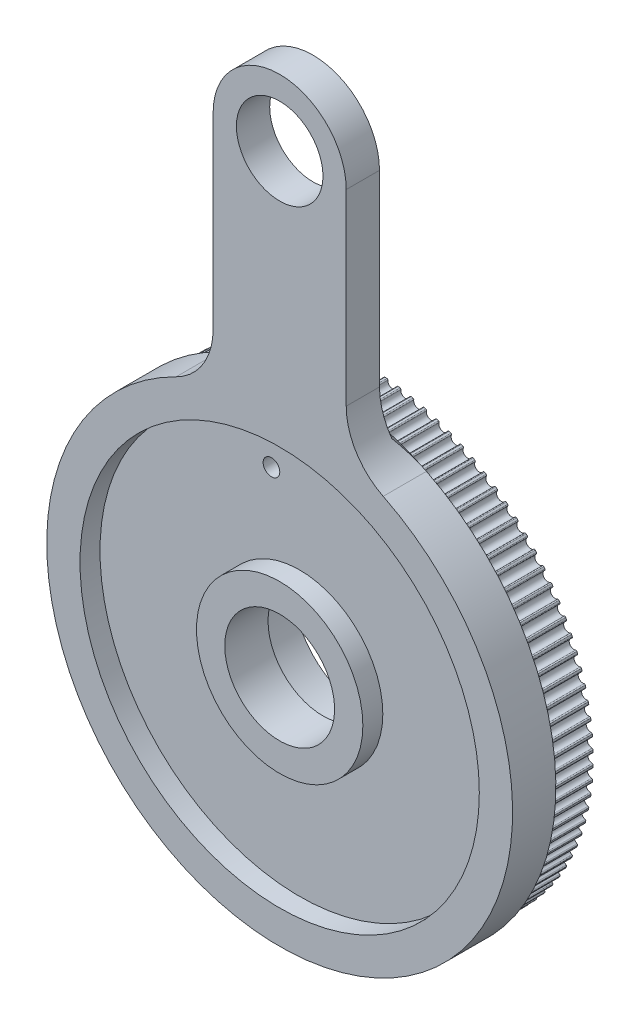
SolidWorks part; units mm, degrees
ref_plane "前视基准面" through (0, 0, 0) normal (0, 0, 1) x (1, 0, 0)
ref_plane "上视基准面" through (0, 0, 0) normal (0, 1, 0) x (1, 0, 0)
ref_plane "右视基准面" through (0, 0, 0) normal (1, 0, 0) x (0, 0, -1)
sketch "草图1" plane through (0, 0, 0) normal (0, 0, 1) x (1, 0, 0)
  line L0 (-10, 68.5) -> (-10, 40.3113)
  line L1 (10, 68.5) -> (10, 40.3113)
  arc A0 (-15.5556, 31.3532) -> (15.5556, 31.3532) centre (0, 0) ccw
  circle A1 centre (0, 0) radius 8.25
  circle A2 centre (0, 68.5) radius 6.5
  arc A3 (10, 68.5) -> (-10, 68.5) centre (0, 68.5) ccw
  arc A4 (10, 40.3113) -> (15.5556, 31.3532) centre (20, 40.3113) ccw
  arc A5 (-10, 40.3113) -> (-15.5556, 31.3532) centre (-20, 40.3113) cw
  dimension "D1" = 70
  dimension "D2" = 16.5
  dimension "D3" = 13
  dimension "D5" = 20
  dimension "D6" = 10
  dimension "D4" = 68.5
extrude "凸台-拉伸1" add sketch "草图1" along normal blind 6.5
sketch "草图2" plane through (0, 0, 6.5) normal (0, 0, 1) x (1, 0, 0)
  circle A0 centre (0, 0) radius 12.5
  circle A1 centre (0, 0) radius 30
  dimension "D1" = 60
  dimension "D2" = 25
extrude "切除-拉伸1" cut sketch "草图2" against normal blind 3
sketch "草图3" plane through (0, 0, 0) normal (0, 0, -1) x (-1, 0, 0)
  line L0 (-10, 40.3113) -> (-10, 68.5) construction
  line L1 (10, 68.5) -> (10, 40.3113) construction
  line L2 (-10, 40.3113) -> (-10, 68.5)
  line L3 (10, 68.5) -> (10, 40.3113)
  arc A1 (10, 68.5) -> (-10, 68.5) centre (0, 68.5) ccw construction
  arc A2 (15.5556, 31.3532) -> (-15.5556, 31.3532) centre (0, 0) ccw
  arc A3 (10, 68.5) -> (-10, 68.5) centre (0, 68.5) ccw
  arc A4 (-15.5556, 31.3532) -> (15.5556, 31.3532) centre (0, 0) ccw construction
  arc A5 (10, 40.3113) -> (15.5556, 31.3532) centre (20, 40.3113) ccw construction
  arc A6 (-15.5556, 31.3532) -> (-10, 40.3113) centre (-20, 40.3113) ccw construction
  arc A7 (10, 40.3113) -> (15.5556, 31.3532) centre (20, 40.3113) ccw
  arc A8 (-15.5556, 31.3532) -> (-10, 40.3113) centre (-20, 40.3113) ccw
extrude "切除-拉伸2" cut sketch "草图3" against normal blind 1.5
chamfer "倒角1" distance 1.5 angle 45 1 edges at (0, 35, 1.5)
sketch "草图4" plane through (0, 0, 0) normal (0, 0, -1) x (-1, 0, 0)
  arc B0 (1.1216, 34.1041) -> (0.8633, 34.1116) centre (0, 0) ccw
  arc B1 (1.2763, 33.9415) -> (1.1216, 34.1041) centre (1.1163, 33.9441) ccw
  arc B2 (0.8633, 34.1116) -> (0.6994, 33.9583) centre (0.8593, 33.9516) ccw
  arc B3 (1.2763, 33.9415) -> (2.6727, 33.8602) centre (1.9762, 33.93) ccw
  arc B4 (-0.8633, 34.1116) -> (-1.1216, 34.1041) centre (0, 0) ccw
  arc B5 (-0.6994, 33.9583) -> (-0.8633, 34.1116) centre (-0.8593, 33.9516) ccw
  arc B6 (-1.1216, 34.1041) -> (-1.2763, 33.9415) centre (-1.1163, 33.9441) ccw
  arc B7 (-0.6994, 33.9583) -> (0.6994, 33.9583) centre (0, 33.9875) ccw
  arc B8 (-2.8453, 34.0037) -> (-3.1027, 33.9812) centre (0, 0) ccw
  arc B9 (-2.6727, 33.8602) -> (-2.8453, 34.0037) centre (-2.8319, 33.8442) ccw
  arc B10 (-3.1027, 33.9812) -> (-3.2477, 33.8099) centre (-3.0881, 33.8218) ccw
  arc B11 (-2.6727, 33.8602) -> (-1.2763, 33.9415) centre (-1.9762, 33.93) ccw
  arc B12 (-4.8176, 33.7807) -> (-5.0732, 33.7433) centre (0, 0) ccw
  arc B13 (-4.637, 33.6475) -> (-4.8176, 33.7807) centre (-4.795, 33.6223) ccw
  arc B14 (-5.0732, 33.7433) -> (-5.208, 33.5638) centre (-5.0494, 33.585) ccw
  arc B15 (-4.637, 33.6475) -> (-3.2477, 33.8099) centre (-3.9457, 33.7577) ccw
  arc B16 (-6.7736, 33.4434) -> (-7.0266, 33.3912) centre (0, 0) ccw
  arc B17 (-6.5856, 33.321) -> (-6.7736, 33.4434) centre (-6.7418, 33.2866) ccw
  arc B18 (-7.0266, 33.3912) -> (-7.1508, 33.2042) centre (-6.9937, 33.2346) ccw
  arc B19 (-6.5856, 33.321) -> (-5.208, 33.5638) centre (-5.9019, 33.4712) ccw
  arc B20 (-8.7067, 32.993) -> (-8.9563, 32.9261) centre (0, 0) ccw
  arc B21 (-8.5119, 32.8817) -> (-8.7067, 32.993) centre (-8.6659, 32.8383) ccw
  arc B22 (-8.9563, 32.9261) -> (-9.0693, 32.7323) centre (-8.9143, 32.7717) ccw
  arc B23 (-8.5119, 32.8817) -> (-7.1508, 33.2042) centre (-7.8381, 33.0714) ccw
  arc B24 (-10.6103, 32.4309) -> (-10.8556, 32.3497) centre (0, 0) ccw
  arc B25 (-10.4094, 32.3311) -> (-10.6103, 32.4309) centre (-10.5606, 32.2789) ccw
  arc B26 (-10.8556, 32.3497) -> (-10.9572, 32.1496) centre (-10.8047, 32.198) ccw
  arc B27 (-10.4094, 32.3311) -> (-9.0693, 32.7323) centre (-9.7477, 32.5597) ccw
  arc B28 (-12.4781, 31.7591) -> (-12.7182, 31.6637) centre (0, 0) ccw
  arc B29 (-12.2716, 31.6712) -> (-12.4781, 31.7591) centre (-12.4196, 31.6102) ccw
  arc B30 (-12.7182, 31.6637) -> (-12.808, 31.4581) centre (-12.6586, 31.5153) ccw
  arc B31 (-12.2716, 31.6712) -> (-10.9572, 32.1496) centre (-11.6244, 31.9378) ccw
  arc B32 (-14.3036, 30.9799) -> (-14.5378, 30.8707) centre (0, 0) ccw
  arc B33 (-14.0924, 30.904) -> (-14.3036, 30.9799) centre (-14.2365, 30.8346) ccw
  arc B34 (-14.5378, 30.8707) -> (-14.6155, 30.6601) centre (-14.4696, 30.7259) ccw
  arc B35 (-14.0924, 30.904) -> (-12.808, 31.4581) centre (-13.4618, 31.2079) ccw
  arc B36 (-16.0807, 30.0958) -> (-16.3081, 29.9731) centre (0, 0) ccw
  arc B37 (-15.8655, 30.0324) -> (-16.0807, 30.0958) centre (-16.0053, 29.9547) ccw
  arc B38 (-16.3081, 29.9731) -> (-16.3735, 29.7584) centre (-16.2317, 29.8326) ccw
  arc B39 (-15.8655, 30.0324) -> (-14.6155, 30.6601) centre (-15.2536, 30.3723) ccw
  arc B40 (-17.8034, 29.1098) -> (-18.0233, 28.9742) centre (0, 0) ccw
  arc B41 (-17.5848, 29.0591) -> (-17.8034, 29.1098) centre (-17.7199, 28.9733) ccw
  arc B42 (-18.0233, 28.9742) -> (-18.0761, 28.7561) centre (-17.9388, 28.8383) ccw
  arc B43 (-17.5848, 29.0591) -> (-16.3735, 29.7584) centre (-16.9937, 29.434) ccw
  arc B44 (-19.4659, 28.0254) -> (-19.6775, 27.8772) centre (0, 0) ccw
  arc B45 (-19.2447, 27.9874) -> (-19.4659, 28.0254) centre (-19.3746, 27.894) ccw
  arc B46 (-19.6775, 27.8772) -> (-19.7175, 27.6564) centre (-19.5853, 27.7465) ccw
  arc B47 (-19.2447, 27.9874) -> (-18.0761, 28.7561) centre (-18.6764, 28.3961) ccw
  arc B48 (-21.0625, 26.8462) -> (-21.2652, 26.6859) centre (0, 0) ccw
  arc B49 (-20.8395, 26.8211) -> (-21.0625, 26.8462) centre (-20.9637, 26.7203) ccw
  arc B50 (-21.2652, 26.6859) -> (-21.2922, 26.4631) centre (-21.1655, 26.5608) ccw
  arc B51 (-20.8395, 26.8211) -> (-19.7175, 27.6564) centre (-20.2959, 27.2622) ccw
  arc B52 (-22.5878, 25.5761) -> (-22.7808, 25.4043) centre (0, 0) ccw
  arc B53 (-22.3637, 25.564) -> (-22.5878, 25.5761) centre (-22.4819, 25.4561) ccw
  arc B54 (-22.7808, 25.4043) -> (-22.7949, 25.1803) centre (-22.674, 25.2852) ccw
  arc B55 (-22.3637, 25.564) -> (-21.2922, 26.4631) centre (-21.8467, 26.0359) ccw
  arc B56 (-24.0367, 24.2194) -> (-24.2194, 24.0367) centre (0, 0) ccw
  arc B57 (-23.8123, 24.2204) -> (-24.0367, 24.2194) centre (-23.924, 24.1059) ccw
  arc B58 (-24.2194, 24.0367) -> (-24.2204, 23.8123) centre (-24.1059, 23.924) ccw
  arc B59 (-23.8123, 24.2204) -> (-22.7949, 25.1803) centre (-23.3236, 24.7216) ccw
  arc B60 (-25.4043, 22.7808) -> (-25.5761, 22.5878) centre (0, 0) ccw
  arc B61 (-25.1803, 22.7949) -> (-25.4043, 22.7808) centre (-25.2852, 22.674) ccw
  arc B62 (-25.5761, 22.5878) -> (-25.564, 22.3637) centre (-25.4561, 22.4819) ccw
  arc B63 (-25.1803, 22.7949) -> (-24.2204, 23.8123) centre (-24.7216, 23.3236) ccw
  arc B64 (-26.6859, 21.2652) -> (-26.8462, 21.0625) centre (0, 0) ccw
  arc B65 (-26.4631, 21.2922) -> (-26.6859, 21.2652) centre (-26.5608, 21.1655) ccw
  arc B66 (-26.8462, 21.0625) -> (-26.8211, 20.8395) centre (-26.7203, 20.9637) ccw
  arc B67 (-26.4631, 21.2922) -> (-25.564, 22.3637) centre (-26.0359, 21.8467) ccw
  arc B68 (-27.8772, 19.6775) -> (-28.0254, 19.4659) centre (0, 0) ccw
  arc B69 (-27.6564, 19.7175) -> (-27.8772, 19.6775) centre (-27.7465, 19.5853) ccw
  arc B70 (-28.0254, 19.4659) -> (-27.9874, 19.2447) centre (-27.894, 19.3746) ccw
  arc B71 (-27.6564, 19.7175) -> (-26.8211, 20.8395) centre (-27.2622, 20.2959) ccw
  arc B72 (-28.9742, 18.0233) -> (-29.1098, 17.8034) centre (0, 0) ccw
  arc B73 (-28.7561, 18.0761) -> (-28.9742, 18.0233) centre (-28.8383, 17.9388) ccw
  arc B74 (-29.1098, 17.8034) -> (-29.0591, 17.5848) centre (-28.9733, 17.7199) ccw
  arc B75 (-28.7561, 18.0761) -> (-27.9874, 19.2447) centre (-28.3961, 18.6764) ccw
  arc B76 (-29.9731, 16.3081) -> (-30.0958, 16.0807) centre (0, 0) ccw
  arc B77 (-29.7584, 16.3735) -> (-29.9731, 16.3081) centre (-29.8326, 16.2317) ccw
  arc B78 (-30.0958, 16.0807) -> (-30.0324, 15.8655) centre (-29.9547, 16.0053) ccw
  arc B79 (-29.7584, 16.3735) -> (-29.0591, 17.5848) centre (-29.434, 16.9937) ccw
  arc B80 (-30.8707, 14.5378) -> (-30.9799, 14.3036) centre (0, 0) ccw
  arc B81 (-30.6601, 14.6155) -> (-30.8707, 14.5378) centre (-30.7259, 14.4696) ccw
  arc B82 (-30.9799, 14.3036) -> (-30.904, 14.0924) centre (-30.8346, 14.2365) ccw
  arc B83 (-30.6601, 14.6155) -> (-30.0324, 15.8655) centre (-30.3723, 15.2536) ccw
  arc B84 (-31.6637, 12.7182) -> (-31.7591, 12.4781) centre (0, 0) ccw
  arc B85 (-31.4581, 12.808) -> (-31.6637, 12.7182) centre (-31.5153, 12.6586) ccw
  arc B86 (-31.7591, 12.4781) -> (-31.6712, 12.2716) centre (-31.6102, 12.4196) ccw
  arc B87 (-31.4581, 12.808) -> (-30.904, 14.0924) centre (-31.2079, 13.4618) ccw
  arc B88 (-32.3497, 10.8556) -> (-32.4309, 10.6103) centre (0, 0) ccw
  arc B89 (-32.1496, 10.9572) -> (-32.3497, 10.8556) centre (-32.198, 10.8047) ccw
  arc B90 (-32.4309, 10.6103) -> (-32.3311, 10.4094) centre (-32.2789, 10.5606) ccw
  arc B91 (-32.1496, 10.9572) -> (-31.6712, 12.2716) centre (-31.9378, 11.6244) ccw
  arc B92 (-32.9261, 8.9563) -> (-32.993, 8.7067) centre (0, 0) ccw
  arc B93 (-32.7323, 9.0693) -> (-32.9261, 8.9563) centre (-32.7717, 8.9143) ccw
  arc B94 (-32.993, 8.7067) -> (-32.8817, 8.5119) centre (-32.8383, 8.6659) ccw
  arc B95 (-32.7323, 9.0693) -> (-32.3311, 10.4094) centre (-32.5597, 9.7477) ccw
  arc B96 (-33.3912, 7.0266) -> (-33.4434, 6.7736) centre (0, 0) ccw
  arc B97 (-33.2042, 7.1508) -> (-33.3912, 7.0266) centre (-33.2346, 6.9937) ccw
  arc B98 (-33.4434, 6.7736) -> (-33.321, 6.5856) centre (-33.2866, 6.7418) ccw
  arc B99 (-33.2042, 7.1508) -> (-32.8817, 8.5119) centre (-33.0714, 7.8381) ccw
  arc B100 (-33.7433, 5.0732) -> (-33.7807, 4.8176) centre (0, 0) ccw
  arc B101 (-33.5638, 5.208) -> (-33.7433, 5.0732) centre (-33.585, 5.0494) ccw
  arc B102 (-33.7807, 4.8176) -> (-33.6475, 4.637) centre (-33.6223, 4.795) ccw
  arc B103 (-33.5638, 5.208) -> (-33.321, 6.5856) centre (-33.4712, 5.9019) ccw
  arc B104 (-33.9812, 3.1027) -> (-34.0037, 2.8453) centre (0, 0) ccw
  arc B105 (-33.8099, 3.2477) -> (-33.9812, 3.1027) centre (-33.8218, 3.0881) ccw
  arc B106 (-34.0037, 2.8453) -> (-33.8602, 2.6727) centre (-33.8442, 2.8319) ccw
  arc B107 (-33.8099, 3.2477) -> (-33.6475, 4.637) centre (-33.7577, 3.9457) ccw
  arc B108 (-34.1041, 1.1216) -> (-34.1116, 0.8633) centre (0, 0) ccw
  arc B109 (-33.9415, 1.2763) -> (-34.1041, 1.1216) centre (-33.9441, 1.1163) ccw
  arc B110 (-34.1116, 0.8633) -> (-33.9583, 0.6994) centre (-33.9516, 0.8593) ccw
  arc B111 (-33.9415, 1.2763) -> (-33.8602, 2.6727) centre (-33.93, 1.9762) ccw
  arc B112 (-34.1116, -0.8633) -> (-34.1041, -1.1216) centre (0, 0) ccw
  arc B113 (-33.9583, -0.6994) -> (-34.1116, -0.8633) centre (-33.9516, -0.8593) ccw
  arc B114 (-34.1041, -1.1216) -> (-33.9415, -1.2763) centre (-33.9441, -1.1163) ccw
  arc B115 (-33.9583, -0.6994) -> (-33.9583, 0.6994) centre (-33.9875, 0) ccw
  arc B116 (-34.0037, -2.8453) -> (-33.9812, -3.1027) centre (0, 0) ccw
  arc B117 (-33.8602, -2.6727) -> (-34.0037, -2.8453) centre (-33.8442, -2.8319) ccw
  arc B118 (-33.9812, -3.1027) -> (-33.8099, -3.2477) centre (-33.8218, -3.0881) ccw
  arc B119 (-33.8602, -2.6727) -> (-33.9415, -1.2763) centre (-33.93, -1.9762) ccw
  arc B120 (-33.7807, -4.8176) -> (-33.7433, -5.0732) centre (0, 0) ccw
  arc B121 (-33.6475, -4.637) -> (-33.7807, -4.8176) centre (-33.6223, -4.795) ccw
  arc B122 (-33.7433, -5.0732) -> (-33.5638, -5.208) centre (-33.585, -5.0494) ccw
  arc B123 (-33.6475, -4.637) -> (-33.8099, -3.2477) centre (-33.7577, -3.9457) ccw
  arc B124 (-33.4434, -6.7736) -> (-33.3912, -7.0266) centre (0, 0) ccw
  arc B125 (-33.321, -6.5856) -> (-33.4434, -6.7736) centre (-33.2866, -6.7418) ccw
  arc B126 (-33.3912, -7.0266) -> (-33.2042, -7.1508) centre (-33.2346, -6.9937) ccw
  arc B127 (-33.321, -6.5856) -> (-33.5638, -5.208) centre (-33.4712, -5.9019) ccw
  arc B128 (-32.993, -8.7067) -> (-32.9261, -8.9563) centre (0, 0) ccw
  arc B129 (-32.8817, -8.5119) -> (-32.993, -8.7067) centre (-32.8383, -8.6659) ccw
  arc B130 (-32.9261, -8.9563) -> (-32.7323, -9.0693) centre (-32.7717, -8.9143) ccw
  arc B131 (-32.8817, -8.5119) -> (-33.2042, -7.1508) centre (-33.0714, -7.8381) ccw
  arc B132 (-32.4309, -10.6103) -> (-32.3497, -10.8556) centre (0, 0) ccw
  arc B133 (-32.3311, -10.4094) -> (-32.4309, -10.6103) centre (-32.2789, -10.5606) ccw
  arc B134 (-32.3497, -10.8556) -> (-32.1496, -10.9572) centre (-32.198, -10.8047) ccw
  arc B135 (-32.3311, -10.4094) -> (-32.7323, -9.0693) centre (-32.5597, -9.7477) ccw
  arc B136 (-31.7591, -12.4781) -> (-31.6637, -12.7182) centre (0, 0) ccw
  arc B137 (-31.6712, -12.2716) -> (-31.7591, -12.4781) centre (-31.6102, -12.4196) ccw
  arc B138 (-31.6637, -12.7182) -> (-31.4581, -12.808) centre (-31.5153, -12.6586) ccw
  arc B139 (-31.6712, -12.2716) -> (-32.1496, -10.9572) centre (-31.9378, -11.6244) ccw
  arc B140 (-30.9799, -14.3036) -> (-30.8707, -14.5378) centre (0, 0) ccw
  arc B141 (-30.904, -14.0924) -> (-30.9799, -14.3036) centre (-30.8346, -14.2365) ccw
  arc B142 (-30.8707, -14.5378) -> (-30.6601, -14.6155) centre (-30.7259, -14.4696) ccw
  arc B143 (-30.904, -14.0924) -> (-31.4581, -12.808) centre (-31.2079, -13.4618) ccw
  arc B144 (-30.0958, -16.0807) -> (-29.9731, -16.3081) centre (0, 0) ccw
  arc B145 (-30.0324, -15.8655) -> (-30.0958, -16.0807) centre (-29.9547, -16.0053) ccw
  arc B146 (-29.9731, -16.3081) -> (-29.7584, -16.3735) centre (-29.8326, -16.2317) ccw
  arc B147 (-30.0324, -15.8655) -> (-30.6601, -14.6155) centre (-30.3723, -15.2536) ccw
  arc B148 (-29.1098, -17.8034) -> (-28.9742, -18.0233) centre (0, 0) ccw
  arc B149 (-29.0591, -17.5848) -> (-29.1098, -17.8034) centre (-28.9733, -17.7199) ccw
  arc B150 (-28.9742, -18.0233) -> (-28.7561, -18.0761) centre (-28.8383, -17.9388) ccw
  arc B151 (-29.0591, -17.5848) -> (-29.7584, -16.3735) centre (-29.434, -16.9938) ccw
  arc B152 (-28.0254, -19.4659) -> (-27.8772, -19.6775) centre (0, 0) ccw
  arc B153 (-27.9874, -19.2447) -> (-28.0254, -19.4659) centre (-27.894, -19.3746) ccw
  arc B154 (-27.8772, -19.6775) -> (-27.6564, -19.7175) centre (-27.7465, -19.5853) ccw
  arc B155 (-27.9874, -19.2447) -> (-28.7561, -18.0761) centre (-28.3961, -18.6764) ccw
  arc B156 (-26.8462, -21.0625) -> (-26.6859, -21.2652) centre (0, 0) ccw
  arc B157 (-26.8211, -20.8395) -> (-26.8462, -21.0625) centre (-26.7203, -20.9637) ccw
  arc B158 (-26.6859, -21.2652) -> (-26.4631, -21.2922) centre (-26.5608, -21.1655) ccw
  arc B159 (-26.8211, -20.8395) -> (-27.6564, -19.7175) centre (-27.2622, -20.2959) ccw
  arc B160 (-25.5761, -22.5878) -> (-25.4043, -22.7808) centre (0, 0) ccw
  arc B161 (-25.564, -22.3637) -> (-25.5761, -22.5878) centre (-25.4561, -22.4819) ccw
  arc B162 (-25.4043, -22.7808) -> (-25.1803, -22.7949) centre (-25.2852, -22.674) ccw
  arc B163 (-25.564, -22.3637) -> (-26.4631, -21.2922) centre (-26.0359, -21.8467) ccw
  arc B164 (-24.2194, -24.0367) -> (-24.0367, -24.2194) centre (0, 0) ccw
  arc B165 (-24.2204, -23.8123) -> (-24.2194, -24.0367) centre (-24.1059, -23.924) ccw
  arc B166 (-24.0367, -24.2194) -> (-23.8123, -24.2204) centre (-23.924, -24.1059) ccw
  arc B167 (-24.2204, -23.8123) -> (-25.1803, -22.7949) centre (-24.7216, -23.3236) ccw
  arc B168 (-22.7808, -25.4043) -> (-22.5878, -25.5761) centre (0, 0) ccw
  arc B169 (-22.7949, -25.1803) -> (-22.7808, -25.4043) centre (-22.674, -25.2852) ccw
  arc B170 (-22.5878, -25.5761) -> (-22.3637, -25.564) centre (-22.4819, -25.4561) ccw
  arc B171 (-22.7949, -25.1803) -> (-23.8123, -24.2204) centre (-23.3236, -24.7216) ccw
  arc B172 (-21.2652, -26.6859) -> (-21.0625, -26.8462) centre (0, 0) ccw
  arc B173 (-21.2922, -26.4631) -> (-21.2652, -26.6859) centre (-21.1655, -26.5608) ccw
  arc B174 (-21.0625, -26.8462) -> (-20.8395, -26.8211) centre (-20.9637, -26.7203) ccw
  arc B175 (-21.2922, -26.4631) -> (-22.3637, -25.564) centre (-21.8467, -26.0359) ccw
  arc B176 (-19.6775, -27.8772) -> (-19.4659, -28.0254) centre (0, 0) ccw
  arc B177 (-19.7175, -27.6564) -> (-19.6775, -27.8772) centre (-19.5853, -27.7465) ccw
  arc B178 (-19.4659, -28.0254) -> (-19.2447, -27.9874) centre (-19.3746, -27.894) ccw
  arc B179 (-19.7175, -27.6564) -> (-20.8395, -26.8211) centre (-20.2959, -27.2622) ccw
  arc B180 (-18.0233, -28.9742) -> (-17.8034, -29.1098) centre (0, 0) ccw
  arc B181 (-18.0761, -28.7561) -> (-18.0233, -28.9742) centre (-17.9388, -28.8383) ccw
  arc B182 (-17.8034, -29.1098) -> (-17.5848, -29.0591) centre (-17.7199, -28.9733) ccw
  arc B183 (-18.0761, -28.7561) -> (-19.2447, -27.9874) centre (-18.6764, -28.3961) ccw
  arc B184 (-16.3081, -29.9731) -> (-16.0807, -30.0958) centre (0, 0) ccw
  arc B185 (-16.3735, -29.7584) -> (-16.3081, -29.9731) centre (-16.2317, -29.8326) ccw
  arc B186 (-16.0807, -30.0958) -> (-15.8655, -30.0324) centre (-16.0053, -29.9547) ccw
  arc B187 (-16.3735, -29.7584) -> (-17.5848, -29.0591) centre (-16.9937, -29.434) ccw
  arc B188 (-14.5378, -30.8707) -> (-14.3036, -30.9799) centre (0, 0) ccw
  arc B189 (-14.6155, -30.6601) -> (-14.5378, -30.8707) centre (-14.4696, -30.7259) ccw
  arc B190 (-14.3036, -30.9799) -> (-14.0924, -30.904) centre (-14.2365, -30.8346) ccw
  arc B191 (-14.6155, -30.6601) -> (-15.8655, -30.0324) centre (-15.2536, -30.3723) ccw
  arc B192 (-12.7182, -31.6637) -> (-12.4781, -31.7591) centre (0, 0) ccw
  arc B193 (-12.808, -31.4581) -> (-12.7182, -31.6637) centre (-12.6586, -31.5153) ccw
  arc B194 (-12.4781, -31.7591) -> (-12.2716, -31.6712) centre (-12.4196, -31.6102) ccw
  arc B195 (-12.808, -31.4581) -> (-14.0924, -30.904) centre (-13.4618, -31.2079) ccw
  arc B196 (-10.8556, -32.3497) -> (-10.6103, -32.4309) centre (0, 0) ccw
  arc B197 (-10.9572, -32.1496) -> (-10.8556, -32.3497) centre (-10.8047, -32.198) ccw
  arc B198 (-10.6103, -32.4309) -> (-10.4094, -32.3311) centre (-10.5606, -32.2789) ccw
  arc B199 (-10.9572, -32.1496) -> (-12.2716, -31.6712) centre (-11.6244, -31.9378) ccw
  arc B200 (-8.9563, -32.9261) -> (-8.7067, -32.993) centre (0, 0) ccw
  arc B201 (-9.0693, -32.7323) -> (-8.9563, -32.9261) centre (-8.9143, -32.7717) ccw
  arc B202 (-8.7067, -32.993) -> (-8.5119, -32.8817) centre (-8.6659, -32.8383) ccw
  arc B203 (-9.0693, -32.7323) -> (-10.4094, -32.3311) centre (-9.7477, -32.5597) ccw
  arc B204 (-7.0266, -33.3912) -> (-6.7736, -33.4434) centre (0, 0) ccw
  arc B205 (-7.1508, -33.2042) -> (-7.0266, -33.3912) centre (-6.9937, -33.2346) ccw
  arc B206 (-6.7736, -33.4434) -> (-6.5856, -33.321) centre (-6.7418, -33.2866) ccw
  arc B207 (-7.1508, -33.2042) -> (-8.5119, -32.8817) centre (-7.8381, -33.0714) ccw
  arc B208 (-5.0732, -33.7433) -> (-4.8176, -33.7807) centre (0, 0) ccw
  arc B209 (-5.208, -33.5638) -> (-5.0732, -33.7433) centre (-5.0494, -33.585) ccw
  arc B210 (-4.8176, -33.7807) -> (-4.637, -33.6475) centre (-4.795, -33.6223) ccw
  arc B211 (-5.208, -33.5638) -> (-6.5856, -33.321) centre (-5.9019, -33.4712) ccw
  arc B212 (-3.1027, -33.9812) -> (-2.8453, -34.0037) centre (0, 0) ccw
  arc B213 (-3.2477, -33.8099) -> (-3.1027, -33.9812) centre (-3.0881, -33.8218) ccw
  arc B214 (-2.8453, -34.0037) -> (-2.6727, -33.8602) centre (-2.8319, -33.8442) ccw
  arc B215 (-3.2477, -33.8099) -> (-4.637, -33.6475) centre (-3.9457, -33.7577) ccw
  arc B216 (-1.1216, -34.1041) -> (-0.8633, -34.1116) centre (0, 0) ccw
  arc B217 (-1.2763, -33.9415) -> (-1.1216, -34.1041) centre (-1.1163, -33.9441) ccw
  arc B218 (-0.8633, -34.1116) -> (-0.6994, -33.9583) centre (-0.8593, -33.9516) ccw
  arc B219 (-1.2763, -33.9415) -> (-2.6727, -33.8602) centre (-1.9762, -33.93) ccw
  arc B220 (0.8633, -34.1116) -> (1.1216, -34.1041) centre (0, 0) ccw
  arc B221 (0.6994, -33.9583) -> (0.8633, -34.1116) centre (0.8593, -33.9516) ccw
  arc B222 (1.1216, -34.1041) -> (1.2763, -33.9415) centre (1.1163, -33.9441) ccw
  arc B223 (0.6994, -33.9583) -> (-0.6994, -33.9583) centre (0, -33.9875) ccw
  arc B224 (2.8453, -34.0037) -> (3.1027, -33.9812) centre (0, 0) ccw
  arc B225 (2.6727, -33.8602) -> (2.8453, -34.0037) centre (2.8319, -33.8442) ccw
  arc B226 (3.1027, -33.9812) -> (3.2477, -33.8099) centre (3.0881, -33.8218) ccw
  arc B227 (2.6727, -33.8602) -> (1.2763, -33.9415) centre (1.9762, -33.93) ccw
  arc B228 (4.8176, -33.7807) -> (5.0732, -33.7433) centre (0, 0) ccw
  arc B229 (4.637, -33.6475) -> (4.8176, -33.7807) centre (4.795, -33.6223) ccw
  arc B230 (5.0732, -33.7433) -> (5.208, -33.5638) centre (5.0494, -33.585) ccw
  arc B231 (4.637, -33.6475) -> (3.2477, -33.8099) centre (3.9457, -33.7577) ccw
  arc B232 (6.7736, -33.4434) -> (7.0266, -33.3912) centre (0, 0) ccw
  arc B233 (6.5856, -33.321) -> (6.7736, -33.4434) centre (6.7418, -33.2866) ccw
  arc B234 (7.0266, -33.3912) -> (7.1508, -33.2042) centre (6.9937, -33.2346) ccw
  arc B235 (6.5856, -33.321) -> (5.208, -33.5638) centre (5.9019, -33.4712) ccw
  arc B236 (8.7067, -32.993) -> (8.9563, -32.9261) centre (0, 0) ccw
  arc B237 (8.5119, -32.8817) -> (8.7067, -32.993) centre (8.6659, -32.8383) ccw
  arc B238 (8.9563, -32.9261) -> (9.0693, -32.7323) centre (8.9143, -32.7717) ccw
  arc B239 (8.5119, -32.8817) -> (7.1508, -33.2042) centre (7.8381, -33.0714) ccw
  arc B240 (10.6103, -32.4309) -> (10.8556, -32.3497) centre (0, 0) ccw
  arc B241 (10.4094, -32.3311) -> (10.6103, -32.4309) centre (10.5606, -32.2789) ccw
  arc B242 (10.8556, -32.3497) -> (10.9572, -32.1496) centre (10.8047, -32.198) ccw
  arc B243 (10.4094, -32.3311) -> (9.0693, -32.7323) centre (9.7477, -32.5597) ccw
  arc B244 (12.4781, -31.7591) -> (12.7182, -31.6637) centre (0, 0) ccw
  arc B245 (12.2716, -31.6712) -> (12.4781, -31.7591) centre (12.4196, -31.6102) ccw
  arc B246 (12.7182, -31.6637) -> (12.808, -31.4581) centre (12.6586, -31.5153) ccw
  arc B247 (12.2716, -31.6712) -> (10.9572, -32.1496) centre (11.6244, -31.9378) ccw
  arc B248 (14.3036, -30.9799) -> (14.5378, -30.8707) centre (0, 0) ccw
  arc B249 (14.0924, -30.904) -> (14.3036, -30.9799) centre (14.2365, -30.8346) ccw
  arc B250 (14.5378, -30.8707) -> (14.6155, -30.6601) centre (14.4696, -30.7259) ccw
  arc B251 (14.0924, -30.904) -> (12.808, -31.4581) centre (13.4618, -31.2079) ccw
  arc B252 (16.0807, -30.0958) -> (16.3081, -29.9731) centre (0, 0) ccw
  arc B253 (15.8655, -30.0324) -> (16.0807, -30.0958) centre (16.0053, -29.9547) ccw
  arc B254 (16.3081, -29.9731) -> (16.3735, -29.7584) centre (16.2317, -29.8326) ccw
  arc B255 (15.8655, -30.0324) -> (14.6155, -30.6601) centre (15.2536, -30.3723) ccw
  arc B256 (17.8034, -29.1098) -> (18.0233, -28.9742) centre (0, 0) ccw
  arc B257 (17.5848, -29.0591) -> (17.8034, -29.1098) centre (17.7199, -28.9733) ccw
  arc B258 (18.0233, -28.9742) -> (18.0761, -28.7561) centre (17.9388, -28.8383) ccw
  arc B259 (17.5848, -29.0591) -> (16.3735, -29.7584) centre (16.9938, -29.434) ccw
  arc B260 (19.4659, -28.0254) -> (19.6775, -27.8772) centre (0, 0) ccw
  arc B261 (19.2447, -27.9874) -> (19.4659, -28.0254) centre (19.3746, -27.894) ccw
  arc B262 (19.6775, -27.8772) -> (19.7175, -27.6564) centre (19.5853, -27.7465) ccw
  arc B263 (19.2447, -27.9874) -> (18.0761, -28.7561) centre (18.6764, -28.3961) ccw
  arc B264 (21.0625, -26.8462) -> (21.2652, -26.6859) centre (0, 0) ccw
  arc B265 (20.8395, -26.8211) -> (21.0625, -26.8462) centre (20.9637, -26.7203) ccw
  arc B266 (21.2652, -26.6859) -> (21.2922, -26.4631) centre (21.1655, -26.5608) ccw
  arc B267 (20.8395, -26.8211) -> (19.7175, -27.6564) centre (20.2959, -27.2622) ccw
  arc B268 (22.5878, -25.5761) -> (22.7808, -25.4043) centre (0, 0) ccw
  arc B269 (22.3637, -25.564) -> (22.5878, -25.5761) centre (22.4819, -25.4561) ccw
  arc B270 (22.7808, -25.4043) -> (22.7949, -25.1803) centre (22.674, -25.2852) ccw
  arc B271 (22.3637, -25.564) -> (21.2922, -26.4631) centre (21.8467, -26.0359) ccw
  arc B272 (24.0367, -24.2194) -> (24.2194, -24.0367) centre (0, 0) ccw
  arc B273 (23.8123, -24.2204) -> (24.0367, -24.2194) centre (23.924, -24.1059) ccw
  arc B274 (24.2194, -24.0367) -> (24.2204, -23.8123) centre (24.1059, -23.924) ccw
  arc B275 (23.8123, -24.2204) -> (22.7949, -25.1803) centre (23.3236, -24.7216) ccw
  arc B276 (25.4043, -22.7808) -> (25.5761, -22.5878) centre (0, 0) ccw
  arc B277 (25.1803, -22.7949) -> (25.4043, -22.7808) centre (25.2852, -22.674) ccw
  arc B278 (25.5761, -22.5878) -> (25.564, -22.3637) centre (25.4561, -22.4819) ccw
  arc B279 (25.1803, -22.7949) -> (24.2204, -23.8123) centre (24.7216, -23.3236) ccw
  arc B280 (26.6859, -21.2652) -> (26.8462, -21.0625) centre (0, 0) ccw
  arc B281 (26.4631, -21.2922) -> (26.6859, -21.2652) centre (26.5608, -21.1655) ccw
  arc B282 (26.8462, -21.0625) -> (26.8211, -20.8395) centre (26.7203, -20.9637) ccw
  arc B283 (26.4631, -21.2922) -> (25.564, -22.3637) centre (26.0359, -21.8467) ccw
  arc B284 (27.8772, -19.6775) -> (28.0254, -19.4659) centre (0, 0) ccw
  arc B285 (27.6564, -19.7175) -> (27.8772, -19.6775) centre (27.7465, -19.5853) ccw
  arc B286 (28.0254, -19.4659) -> (27.9874, -19.2447) centre (27.894, -19.3746) ccw
  arc B287 (27.6564, -19.7175) -> (26.8211, -20.8395) centre (27.2622, -20.2959) ccw
  arc B288 (28.9742, -18.0233) -> (29.1098, -17.8034) centre (0, 0) ccw
  arc B289 (28.7561, -18.0761) -> (28.9742, -18.0233) centre (28.8383, -17.9388) ccw
  arc B290 (29.1098, -17.8034) -> (29.0591, -17.5848) centre (28.9733, -17.7199) ccw
  arc B291 (28.7561, -18.0761) -> (27.9874, -19.2447) centre (28.3961, -18.6764) ccw
  arc B292 (29.9731, -16.3081) -> (30.0958, -16.0807) centre (0, 0) ccw
  arc B293 (29.7584, -16.3735) -> (29.9731, -16.3081) centre (29.8326, -16.2317) ccw
  arc B294 (30.0958, -16.0807) -> (30.0324, -15.8655) centre (29.9547, -16.0053) ccw
  arc B295 (29.7584, -16.3735) -> (29.0591, -17.5848) centre (29.434, -16.9938) ccw
  arc B296 (30.8707, -14.5378) -> (30.9799, -14.3036) centre (0, 0) ccw
  arc B297 (30.6601, -14.6155) -> (30.8707, -14.5378) centre (30.7259, -14.4696) ccw
  arc B298 (30.9799, -14.3036) -> (30.904, -14.0924) centre (30.8346, -14.2365) ccw
  arc B299 (30.6601, -14.6155) -> (30.0324, -15.8655) centre (30.3723, -15.2536) ccw
  arc B300 (31.6637, -12.7182) -> (31.7591, -12.4781) centre (0, 0) ccw
  arc B301 (31.4581, -12.808) -> (31.6637, -12.7182) centre (31.5153, -12.6586) ccw
  arc B302 (31.7591, -12.4781) -> (31.6712, -12.2716) centre (31.6102, -12.4196) ccw
  arc B303 (31.4581, -12.808) -> (30.904, -14.0924) centre (31.2079, -13.4618) ccw
  arc B304 (32.3497, -10.8556) -> (32.4309, -10.6103) centre (0, 0) ccw
  arc B305 (32.1496, -10.9572) -> (32.3497, -10.8556) centre (32.198, -10.8047) ccw
  arc B306 (32.4309, -10.6103) -> (32.3311, -10.4094) centre (32.2789, -10.5606) ccw
  arc B307 (32.1496, -10.9572) -> (31.6712, -12.2716) centre (31.9378, -11.6244) ccw
  arc B308 (32.9261, -8.9563) -> (32.993, -8.7067) centre (0, 0) ccw
  arc B309 (32.7323, -9.0693) -> (32.9261, -8.9563) centre (32.7717, -8.9143) ccw
  arc B310 (32.993, -8.7067) -> (32.8817, -8.5119) centre (32.8383, -8.6659) ccw
  arc B311 (32.7323, -9.0693) -> (32.3311, -10.4094) centre (32.5597, -9.7477) ccw
  arc B312 (33.3912, -7.0266) -> (33.4434, -6.7736) centre (0, 0) ccw
  arc B313 (33.2042, -7.1508) -> (33.3912, -7.0266) centre (33.2346, -6.9937) ccw
  arc B314 (33.4434, -6.7736) -> (33.321, -6.5856) centre (33.2866, -6.7418) ccw
  arc B315 (33.2042, -7.1508) -> (32.8817, -8.5119) centre (33.0714, -7.8381) ccw
  arc B316 (33.7433, -5.0732) -> (33.7807, -4.8176) centre (0, 0) ccw
  arc B317 (33.5638, -5.208) -> (33.7433, -5.0732) centre (33.585, -5.0494) ccw
  arc B318 (33.7807, -4.8176) -> (33.6475, -4.637) centre (33.6223, -4.795) ccw
  arc B319 (33.5638, -5.208) -> (33.321, -6.5856) centre (33.4712, -5.9019) ccw
  arc B320 (33.9812, -3.1027) -> (34.0037, -2.8453) centre (0, 0) ccw
  arc B321 (33.8099, -3.2477) -> (33.9812, -3.1027) centre (33.8218, -3.0881) ccw
  arc B322 (34.0037, -2.8453) -> (33.8602, -2.6727) centre (33.8442, -2.8319) ccw
  arc B323 (33.8099, -3.2477) -> (33.6475, -4.637) centre (33.7577, -3.9457) ccw
  arc B324 (34.1041, -1.1216) -> (34.1116, -0.8633) centre (0, 0) ccw
  arc B325 (33.9415, -1.2763) -> (34.1041, -1.1216) centre (33.9441, -1.1163) ccw
  arc B326 (34.1116, -0.8633) -> (33.9583, -0.6994) centre (33.9516, -0.8593) ccw
  arc B327 (33.9415, -1.2763) -> (33.8602, -2.6727) centre (33.93, -1.9762) ccw
  arc B328 (34.1116, 0.8633) -> (34.1041, 1.1216) centre (0, 0) ccw
  arc B329 (33.9583, 0.6994) -> (34.1116, 0.8633) centre (33.9516, 0.8593) ccw
  arc B330 (34.1041, 1.1216) -> (33.9415, 1.2763) centre (33.9441, 1.1163) ccw
  arc B331 (33.9583, 0.6994) -> (33.9583, -0.6994) centre (33.9875, 0) ccw
  arc B332 (34.0037, 2.8453) -> (33.9812, 3.1027) centre (0, 0) ccw
  arc B333 (33.8602, 2.6727) -> (34.0037, 2.8453) centre (33.8442, 2.8319) ccw
  arc B334 (33.9812, 3.1027) -> (33.8099, 3.2477) centre (33.8218, 3.0881) ccw
  arc B335 (33.8602, 2.6727) -> (33.9415, 1.2763) centre (33.93, 1.9762) ccw
  arc B336 (33.7807, 4.8176) -> (33.7433, 5.0732) centre (0, 0) ccw
  arc B337 (33.6475, 4.637) -> (33.7807, 4.8176) centre (33.6223, 4.795) ccw
  arc B338 (33.7433, 5.0732) -> (33.5638, 5.208) centre (33.585, 5.0494) ccw
  arc B339 (33.6475, 4.637) -> (33.8099, 3.2477) centre (33.7577, 3.9457) ccw
  arc B340 (33.4434, 6.7736) -> (33.3912, 7.0266) centre (0, 0) ccw
  arc B341 (33.321, 6.5856) -> (33.4434, 6.7736) centre (33.2866, 6.7418) ccw
  arc B342 (33.3912, 7.0266) -> (33.2042, 7.1508) centre (33.2346, 6.9937) ccw
  arc B343 (33.321, 6.5856) -> (33.5638, 5.208) centre (33.4712, 5.9019) ccw
  arc B344 (32.993, 8.7067) -> (32.9261, 8.9563) centre (0, 0) ccw
  arc B345 (32.8817, 8.5119) -> (32.993, 8.7067) centre (32.8383, 8.6659) ccw
  arc B346 (32.9261, 8.9563) -> (32.7323, 9.0693) centre (32.7717, 8.9143) ccw
  arc B347 (32.8817, 8.5119) -> (33.2042, 7.1508) centre (33.0714, 7.8381) ccw
  arc B348 (32.4309, 10.6103) -> (32.3497, 10.8556) centre (0, 0) ccw
  arc B349 (32.3311, 10.4094) -> (32.4309, 10.6103) centre (32.2789, 10.5606) ccw
  arc B350 (32.3497, 10.8556) -> (32.1496, 10.9572) centre (32.198, 10.8047) ccw
  arc B351 (32.3311, 10.4094) -> (32.7323, 9.0693) centre (32.5597, 9.7477) ccw
  arc B352 (31.7591, 12.4781) -> (31.6637, 12.7182) centre (0, 0) ccw
  arc B353 (31.6712, 12.2716) -> (31.7591, 12.4781) centre (31.6102, 12.4196) ccw
  arc B354 (31.6637, 12.7182) -> (31.4581, 12.808) centre (31.5153, 12.6586) ccw
  arc B355 (31.6712, 12.2716) -> (32.1496, 10.9572) centre (31.9378, 11.6244) ccw
  arc B356 (30.9799, 14.3036) -> (30.8707, 14.5378) centre (0, 0) ccw
  arc B357 (30.904, 14.0924) -> (30.9799, 14.3036) centre (30.8346, 14.2365) ccw
  arc B358 (30.8707, 14.5378) -> (30.6601, 14.6155) centre (30.7259, 14.4696) ccw
  arc B359 (30.904, 14.0924) -> (31.4581, 12.808) centre (31.2079, 13.4618) ccw
  arc B360 (30.0958, 16.0807) -> (29.9731, 16.3081) centre (0, 0) ccw
  arc B361 (30.0324, 15.8655) -> (30.0958, 16.0807) centre (29.9547, 16.0053) ccw
  arc B362 (29.9731, 16.3081) -> (29.7584, 16.3735) centre (29.8326, 16.2317) ccw
  arc B363 (30.0324, 15.8655) -> (30.6601, 14.6155) centre (30.3723, 15.2536) ccw
  arc B364 (29.1098, 17.8034) -> (28.9742, 18.0233) centre (0, 0) ccw
  arc B365 (29.0591, 17.5848) -> (29.1098, 17.8034) centre (28.9733, 17.7199) ccw
  arc B366 (28.9742, 18.0233) -> (28.7561, 18.0761) centre (28.8383, 17.9388) ccw
  arc B367 (29.0591, 17.5848) -> (29.7584, 16.3735) centre (29.434, 16.9938) ccw
  arc B368 (28.0254, 19.4659) -> (27.8772, 19.6775) centre (0, 0) ccw
  arc B369 (27.9874, 19.2447) -> (28.0254, 19.4659) centre (27.894, 19.3746) ccw
  arc B370 (27.8772, 19.6775) -> (27.6564, 19.7175) centre (27.7465, 19.5853) ccw
  arc B371 (27.9874, 19.2447) -> (28.7561, 18.0761) centre (28.3961, 18.6764) ccw
  arc B372 (26.8462, 21.0625) -> (26.6859, 21.2652) centre (0, 0) ccw
  arc B373 (26.8211, 20.8395) -> (26.8462, 21.0625) centre (26.7203, 20.9637) ccw
  arc B374 (26.6859, 21.2652) -> (26.4631, 21.2922) centre (26.5608, 21.1655) ccw
  arc B375 (26.8211, 20.8395) -> (27.6564, 19.7175) centre (27.2622, 20.2959) ccw
  arc B376 (25.5761, 22.5878) -> (25.4043, 22.7808) centre (0, 0) ccw
  arc B377 (25.564, 22.3637) -> (25.5761, 22.5878) centre (25.4561, 22.4819) ccw
  arc B378 (25.4043, 22.7808) -> (25.1803, 22.7949) centre (25.2852, 22.674) ccw
  arc B379 (25.564, 22.3637) -> (26.4631, 21.2922) centre (26.0359, 21.8467) ccw
  arc B380 (24.2194, 24.0367) -> (24.0367, 24.2194) centre (0, 0) ccw
  arc B381 (24.2204, 23.8123) -> (24.2194, 24.0367) centre (24.1059, 23.924) ccw
  arc B382 (24.0367, 24.2194) -> (23.8123, 24.2204) centre (23.924, 24.1059) ccw
  arc B383 (24.2204, 23.8123) -> (25.1803, 22.7949) centre (24.7216, 23.3236) ccw
  arc B384 (22.7808, 25.4043) -> (22.5878, 25.5761) centre (0, 0) ccw
  arc B385 (22.7949, 25.1803) -> (22.7808, 25.4043) centre (22.674, 25.2852) ccw
  arc B386 (22.5878, 25.5761) -> (22.3637, 25.564) centre (22.4819, 25.4561) ccw
  arc B387 (22.7949, 25.1803) -> (23.8123, 24.2204) centre (23.3236, 24.7216) ccw
  arc B388 (21.2652, 26.6859) -> (21.0625, 26.8462) centre (0, 0) ccw
  arc B389 (21.2922, 26.4631) -> (21.2652, 26.6859) centre (21.1655, 26.5608) ccw
  arc B390 (21.0625, 26.8462) -> (20.8395, 26.8211) centre (20.9637, 26.7203) ccw
  arc B391 (21.2922, 26.4631) -> (22.3637, 25.564) centre (21.8467, 26.0359) ccw
  arc B392 (19.6775, 27.8772) -> (19.4659, 28.0254) centre (0, 0) ccw
  arc B393 (19.7175, 27.6564) -> (19.6775, 27.8772) centre (19.5853, 27.7465) ccw
  arc B394 (19.4659, 28.0254) -> (19.2447, 27.9874) centre (19.3746, 27.894) ccw
  arc B395 (19.7175, 27.6564) -> (20.8395, 26.8211) centre (20.2959, 27.2622) ccw
  arc B396 (18.0233, 28.9742) -> (17.8034, 29.1098) centre (0, 0) ccw
  arc B397 (18.0761, 28.7561) -> (18.0233, 28.9742) centre (17.9388, 28.8383) ccw
  arc B398 (17.8034, 29.1098) -> (17.5848, 29.0591) centre (17.7199, 28.9733) ccw
  arc B399 (18.0761, 28.7561) -> (19.2447, 27.9874) centre (18.6764, 28.3961) ccw
  arc B400 (16.3081, 29.9731) -> (16.0807, 30.0958) centre (0, 0) ccw
  arc B401 (16.3735, 29.7584) -> (16.3081, 29.9731) centre (16.2317, 29.8326) ccw
  arc B402 (16.0807, 30.0958) -> (15.8655, 30.0324) centre (16.0053, 29.9547) ccw
  arc B403 (16.3735, 29.7584) -> (17.5848, 29.0591) centre (16.9937, 29.434) ccw
  arc B404 (14.5378, 30.8707) -> (14.3036, 30.9799) centre (0, 0) ccw
  arc B405 (14.6155, 30.6601) -> (14.5378, 30.8707) centre (14.4696, 30.7259) ccw
  arc B406 (14.3036, 30.9799) -> (14.0924, 30.904) centre (14.2365, 30.8346) ccw
  arc B407 (14.6155, 30.6601) -> (15.8655, 30.0324) centre (15.2536, 30.3723) ccw
  arc B408 (12.7182, 31.6637) -> (12.4781, 31.7591) centre (0, 0) ccw
  arc B409 (12.808, 31.4581) -> (12.7182, 31.6637) centre (12.6586, 31.5153) ccw
  arc B410 (12.4781, 31.7591) -> (12.2716, 31.6712) centre (12.4196, 31.6102) ccw
  arc B411 (12.808, 31.4581) -> (14.0924, 30.904) centre (13.4618, 31.2079) ccw
  arc B412 (10.8556, 32.3497) -> (10.6103, 32.4309) centre (0, 0) ccw
  arc B413 (10.9572, 32.1496) -> (10.8556, 32.3497) centre (10.8047, 32.198) ccw
  arc B414 (10.6103, 32.4309) -> (10.4094, 32.3311) centre (10.5606, 32.2789) ccw
  arc B415 (10.9572, 32.1496) -> (12.2716, 31.6712) centre (11.6244, 31.9378) ccw
  arc B416 (8.9563, 32.9261) -> (8.7067, 32.993) centre (0, 0) ccw
  arc B417 (9.0693, 32.7323) -> (8.9563, 32.9261) centre (8.9143, 32.7717) ccw
  arc B418 (8.7067, 32.993) -> (8.5119, 32.8817) centre (8.6659, 32.8383) ccw
  arc B419 (9.0693, 32.7323) -> (10.4094, 32.3311) centre (9.7477, 32.5597) ccw
  arc B420 (7.0266, 33.3912) -> (6.7736, 33.4434) centre (0, 0) ccw
  arc B421 (7.1508, 33.2042) -> (7.0266, 33.3912) centre (6.9937, 33.2346) ccw
  arc B422 (6.7736, 33.4434) -> (6.5856, 33.321) centre (6.7418, 33.2866) ccw
  arc B423 (7.1508, 33.2042) -> (8.5119, 32.8817) centre (7.8381, 33.0714) ccw
  arc B424 (5.0732, 33.7433) -> (4.8176, 33.7807) centre (0, 0) ccw
  arc B425 (5.208, 33.5638) -> (5.0732, 33.7433) centre (5.0494, 33.585) ccw
  arc B426 (4.8176, 33.7807) -> (4.637, 33.6475) centre (4.795, 33.6223) ccw
  arc B427 (5.208, 33.5638) -> (6.5856, 33.321) centre (5.9019, 33.4712) ccw
  arc B428 (3.1027, 33.9812) -> (2.8453, 34.0037) centre (0, 0) ccw
  arc B429 (3.2477, 33.8099) -> (3.1027, 33.9812) centre (3.0881, 33.8218) ccw
  arc B430 (2.8453, 34.0037) -> (2.6727, 33.8602) centre (2.8319, 33.8442) ccw
  arc B431 (3.2477, 33.8099) -> (4.637, 33.6475) centre (3.9457, 33.7577) ccw
sketch_block_instance "GT2 108齿-1"
sketch_block "GT2 108齿"
extrude "凸台-拉伸2" add sketch "草图4" along normal blind 6.5
sketch "草图6" plane through (0, 0, -6.5) normal (0, 0, -1) x (-1, 0, 0)
  circle A0 centre (0, 0) radius 4
  dimension "D1" = 8
extrude "切除-拉伸3" cut sketch "草图6" against normal through all
sketch "草图7" plane through (0, 0, -6.5) normal (0, 0, -1) x (-1, 0, 0)
  circle A0 centre (0, 0) radius 11.05
  dimension "D1" = 22.1
extrude "切除-拉伸4" cut sketch "草图7" against normal blind 6.5
sketch "草图8" plane through (0, 0, -6.5) normal (0, 0, -1) x (-1, 0, 0)
  circle B0 centre (0, 0) radius 4
  arc B1 (-10, 33.541) -> (10, 33.541) centre (0, 0) ccw
  circle B2 centre (4.2329, 23.7458) radius 2
sketch_block_instance "块1-1"
sketch_block "块1"
sketch "草图9" plane through (0, 0, -6.5) normal (0, 0, -1) x (-1, 0, 0)
  circle A0 centre (4.2329, 23.7458) radius 2 construction
  circle A1 centre (4.2329, 23.7458) radius 2
extrude "切除-拉伸5" cut sketch "草图9" against normal blind 5
sketch "草图10" plane through (0, 0, -1.5) normal (0, 0, -1) x (-1, 0, 0)
  circle A0 centre (4.2329, 23.7458) radius 1.25
  dimension "D1" = 2.5
extrude "切除-拉伸6" cut sketch "草图10" against normal through all
